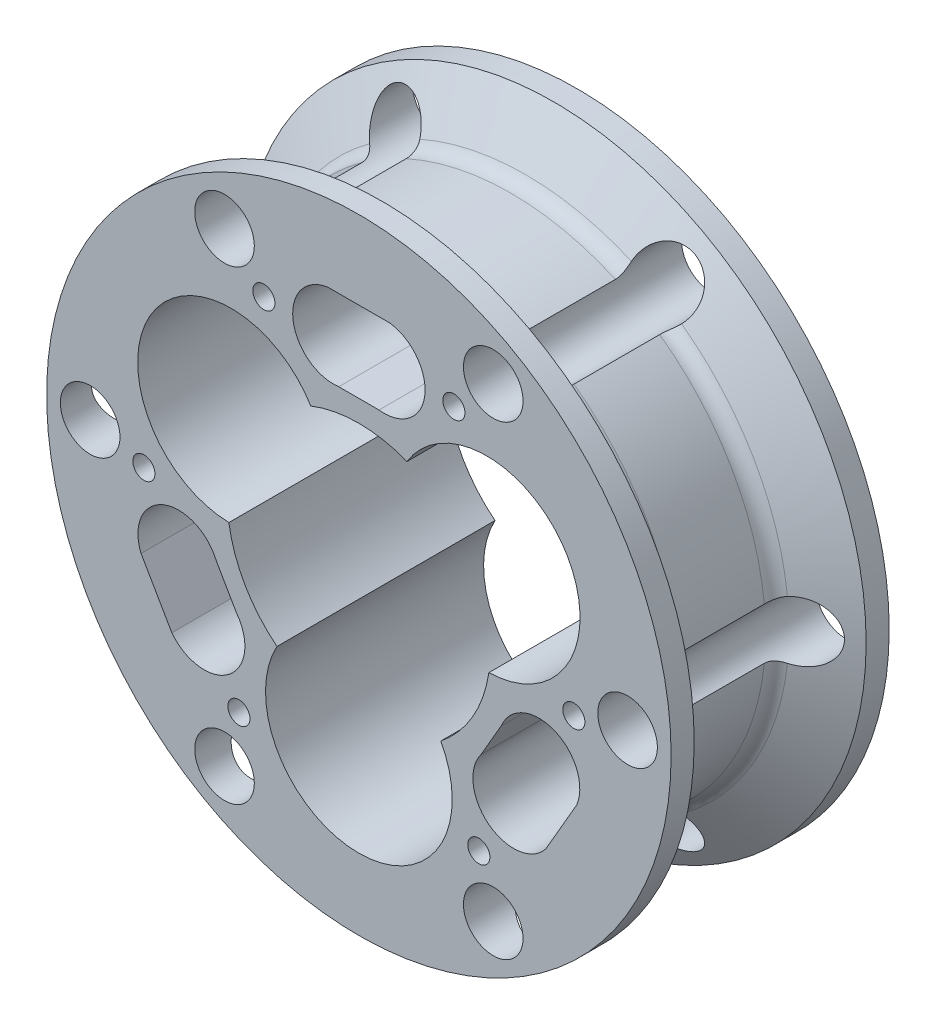
SolidWorks part; units mm, degrees
material "7075-T6, Plate (SS)"
ref_plane "Front Plane" through (0, 0, 0) normal (0, 0, 1) x (1, 0, 0)
ref_plane "Top Plane" through (0, 0, 0) normal (0, 1, 0) x (1, 0, 0)
ref_plane "Right Plane" through (0, 0, 0) normal (1, 0, 0) x (0, 0, -1)
sketch "Sketch1" plane through (0, 0, 0) normal (0, 1, 0) x (1, 0, 0)
  line L0 (42.9895, 30.0228) -> (0, 30.0228)
  line L1 (0, 30.0228) -> (0, 0)
  line L2 (0, 0) -> (42.9895, 0)
  line L3 (42.9895, 0) -> (42.9895, 3.175)
  line L4 (42.9895, 3.175) -> (35.0774, 7.7431)
  line L5 (35.0774, 7.7431) -> (35.0774, 22.2797)
  line L6 (35.0774, 22.2797) -> (42.9895, 26.8478)
  line L7 (42.9895, 26.8478) -> (42.9895, 30.0228)
  line L8 (0, 30.0228) -> (0, 0) construction
revolve "Revolve1" add sketch "Sketch1" angle 360 about L8 reverse direction yes
sketch "Sketch2" plane through (0, 0, -30.0228) normal (0, 0, -1) x (-1, 0, 0)
  line L0 (4.2368, 32.1818) -> (-4.2368, 32.1818)
  line L1 (-2.773, 21.063) -> (2.773, 21.063)
  arc A0 (-4.2368, 32.1818) -> (-2.773, 21.063) centre (-3.5049, 26.6224) ccw
  arc A1 (2.773, 21.063) -> (4.2368, 32.1818) centre (3.5049, 26.6224) ccw
extrude "Cut-Extrude1" cut sketch "Sketch2" against normal through all
sketch "Sketch3" plane through (0, 0, -30.0228) normal (0, 0, -1) x (-1, 0, 0)
  line L0 (25.7518, -19.7601) -> (29.9887, -12.4217)
  line L1 (19.6275, -8.13) -> (16.8546, -12.933)
  arc A0 (29.9887, -12.4217) -> (19.6275, -8.13) centre (24.8081, -10.2759) ccw
  arc A1 (16.8546, -12.933) -> (25.7518, -19.7601) centre (21.3032, -16.3465) ccw
extrude "Cut-Extrude2" cut sketch "Sketch3" against normal through all
sketch "Sketch4" plane through (0, 0, 0) normal (0, 0, 1) x (1, 0, 0)
  line L0 (19.6275, -8.13) -> (16.8546, -12.933)
  line L1 (25.7518, -19.7601) -> (29.9887, -12.4217)
  arc A0 (16.8546, -12.933) -> (25.7518, -19.7601) centre (21.3032, -16.3465) ccw
  arc A1 (29.9887, -12.4217) -> (19.6275, -8.13) centre (24.8081, -10.2759) ccw
extrude "Cut-Extrude3" cut sketch "Sketch4" against normal through all
hole_wizard "M33 Clearance Hole1" positions "Sketch6" profile "Sketch5" hole size "M33" standard "ANSI Metric"
sketch "Sketch6" plane through (0, 0, 0) normal (0, 0, 1) x (1, 0, 0)
  point P0 (0, 0)
sketch "Sketch5" plane through (0, 0, 0) normal (1, 0, 0) x (0, -1, 0)
  line L0 (0, 0) -> (0, 30.0228)
  line L1 (0, 30.0228) -> (18.0975, 30.0228)
  line L2 (18.0975, 30.0228) -> (18.0975, 0)
  line L5 (18.0975, 0) -> (0, 0)
  line L11 (0, -6.35) -> (0, 107.95) construction
  dimension "Thru Hole Dia." = 36.195
  dimension "Thru Hole Depth" = 30.0228
hole_wizard "M2.5 Clearance Hole1" positions "Sketch8" profile "Sketch7" hole size "M2.5" standard "ANSI Metric"
sketch "Sketch8" plane through (0, 0, -30.0228) normal (0, 0, -1) x (-1, 0, 0)
  point P0 (-29.5963, -1.9825)
sketch "Sketch7" plane through (29.5963, -1.9825, -30.0228) normal (1, 0, 0) x (0, 1, 0)
  line L0 (0, 0) -> (0, 30.0228)
  line L1 (0, 30.0228) -> (1.524, 30.0228)
  line L2 (1.524, 30.0228) -> (1.524, 0)
  line L5 (1.524, 0) -> (0, 0)
  line L11 (0, -6.35) -> (0, 107.95) construction
  dimension "Thru Hole Dia." = 3.048
  dimension "Thru Hole Depth" = 30.0228
hole_wizard "M22 Clearance Hole1" positions "Sketch10" profile "Sketch9" hole size "M22" standard "ANSI Metric"
sketch "Sketch10" plane through (0, 0, -30.0228) normal (0, 0, -1) x (-1, 0, 0)
  point P0 (0, -20.32)
  point P1 (-17.5976, 10.16)
sketch "Sketch9" plane through (0, -20.32, -30.0228) normal (1, 0, 0) x (0, 1, 0)
  line L0 (0, 0) -> (0, 30.0228)
  line L1 (0, 30.0228) -> (12.8524, 30.0228)
  line L2 (12.8524, 30.0228) -> (12.8524, 0)
  line L5 (12.8524, 0) -> (0, 0)
  line L11 (0, -6.35) -> (0, 107.95) construction
  dimension "Thru Hole Dia." = 25.7048
  dimension "Thru Hole Depth" = 30.0228
hole_wizard "M22 Clearance Hole2" positions "Sketch12" profile "Sketch11" hole size "M22" standard "ANSI Metric"
sketch "Sketch12" plane through (0, 0, 0) normal (0, 0, 1) x (1, 0, 0)
  point P0 (-17.5976, 10.16)
sketch "Sketch11" plane through (-17.5976, 10.16, 0) normal (1, 0, 0) x (0, -1, 0)
  line L0 (0, 0) -> (0, 30.0228)
  line L1 (0, 30.0228) -> (12.8524, 30.0228)
  line L2 (12.8524, 30.0228) -> (12.8524, 0)
  line L5 (12.8524, 0) -> (0, 0)
  line L11 (0, -6.35) -> (0, 107.95) construction
  dimension "Thru Hole Dia." = 25.7048
  dimension "Thru Hole Depth" = 30.0228
hole_wizard "Hole1" positions "Sketch14" profile "Sketch13" legacy
sketch "Sketch14" plane through (0, 0, 0) normal (0, 0, 1) x (1, 0, 0)
  point P0 (18.4976, -32.0387)
  point P1 (-18.4976, -32.0387)
  point P2 (-36.9951, 0)
  point P3 (-18.4976, 32.0387)
  point P4 (18.4976, 32.0387)
  point P5 (36.9951, 0)
sketch "Sketch13" plane through (18.4976, -32.0387, 0) normal (1, 0, 0) x (0, -1, 0)
  line L0 (0, 0) -> (0, 30.0228)
  line L1 (0, 30.0228) -> (4.1021, 30.0228)
  line L2 (4.1021, 30.0228) -> (4.1021, 0)
  line L3 (4.1021, 0) -> (0, 0)
  line L4 (0, 110) -> (0, -10) construction
  dimension "Diameter" = 8.2042
  dimension "Depth" = 30.0228
hole_wizard "M2.5 Clearance Hole2" positions "Sketch16" profile "Sketch15" hole size "M2.5" standard "ANSI Metric"
sketch "Sketch16" plane through (0, 0, 0) normal (0, 0, 1) x (1, 0, 0)
  point P0 (16.515, -24.6399)
  point P1 (-16.515, -24.6399)
  point P2 (-29.5963, -1.9825)
  point P3 (-13.0812, 26.6224)
  point P4 (13.0812, 26.6224)
sketch "Sketch15" plane through (16.515, -24.6399, 0) normal (1, 0, 0) x (0, -1, 0)
  line L0 (0, 0) -> (0, 30.0228)
  line L1 (0, 30.0228) -> (1.524, 30.0228)
  line L2 (1.524, 30.0228) -> (1.524, 0)
  line L5 (1.524, 0) -> (0, 0)
  line L11 (0, -6.35) -> (0, 107.95) construction
  dimension "Thru Hole Dia." = 3.048
  dimension "Thru Hole Depth" = 30.0228
fillet "Fillet1" radius 2.3622 12 edges at (0, 35.0774, -7.7431) (30.3779, 17.5387, -7.7431) (30.3779, -17.5387, -22.2797) (0, 35.0774, -22.2797) (-30.3779, 17.5387, -7.7431) (0, -35.0774, -7.7431) (30.3779, -17.5387, -7.7431) (-30.3779, -17.5387, -22.2797) (30.3779, 17.5387, -22.2797) (-30.3779, -17.5387, -7.7431) (0, -35.0774, -22.2797) (-30.3779, 17.5387, -22.2797) tangent propagation no
ref_point "Point1"
